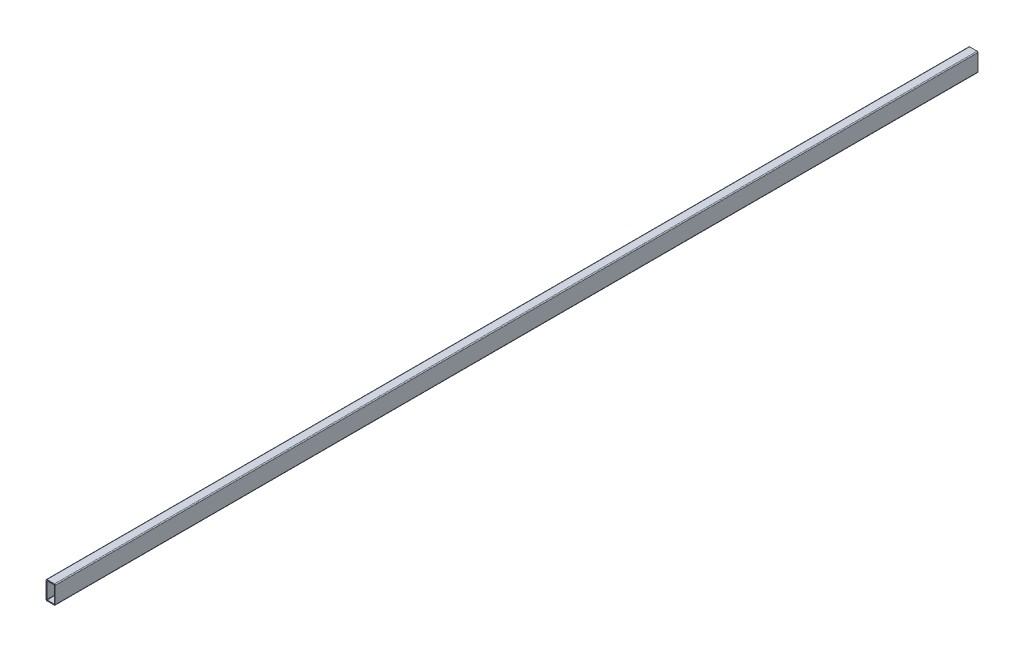
SolidWorks part; units mm, degrees
material "1.0114 (S235J0)"
ref_plane "Płaszczyzna przednia" through (0, 0, 0) normal (0, 0, 1) x (1, 0, 0)
ref_plane "Płaszczyzna górna" through (0, 0, 0) normal (0, 1, 0) x (1, 0, 0)
ref_plane "Płaszczyzna prawa" through (0, 0, 0) normal (1, 0, 0) x (0, 0, -1)
sketch "Szkic1" plane through (0, 0, 0) normal (0, 0, 1) x (1, 0, 0)
  line L0 (-7.1969, 27) -> (14.8031, 27)
  line L1 (-8.1969, -30) -> (15.8031, -30)
  line L2 (-11.1969, -27) -> (-11.1969, 27)
  line L3 (-8.1969, 30) -> (15.8031, 30)
  line L4 (18.8031, -27) -> (18.8031, 27)
  line L5 (15.8031, -26) -> (15.8031, 26)
  line L6 (-7.1969, -27) -> (14.8031, -27)
  line L7 (-8.1969, -26) -> (-8.1969, 26)
  line L8 (-11.1969, 30) -> (18.8031, 30) construction
  line L9 (18.8031, -30) -> (18.8031, 30) construction
  line L10 (-11.1969, -30) -> (18.8031, -30) construction
  line L11 (-11.1969, -30) -> (-11.1969, 30) construction
  line L12 (-8.1969, 27) -> (15.8031, 27) construction
  line L13 (15.8031, -27) -> (15.8031, 27) construction
  line L14 (-8.1969, -27) -> (15.8031, -27) construction
  line L15 (-8.1969, -27) -> (-8.1969, 27) construction
  line L16 (55, 0) -> (-55, 0) construction
  arc A0 (15.8031, 30) -> (18.8031, 27) centre (15.8031, 27) cw
  arc A1 (18.8031, -27) -> (15.8031, -30) centre (15.8031, -27) cw
  arc A2 (-8.1969, -30) -> (-11.1969, -27) centre (-8.1969, -27) cw
  arc A3 (-11.1969, 27) -> (-8.1969, 30) centre (-8.1969, 27) cw
  arc A4 (14.8031, 27) -> (15.8031, 26) centre (14.8031, 26) cw
  arc A5 (15.8031, -26) -> (14.8031, -27) centre (14.8031, -26) cw
  arc A6 (-7.1969, -27) -> (-8.1969, -26) centre (-7.1969, -26) cw
  arc A7 (-8.1969, 26) -> (-7.1969, 27) centre (-7.1969, 26) cw
  point P4 (-11.1969, 0)
  point P12 (15, 0)
  dimension "D4" = 3
  dimension "D1" = 1
  dimension "D2" = 30
  dimension "D5" = 60
  dimension "D3" = 3
extrude "Dodanie-wyciągnięcie1" add sketch "Szkic1" against normal blind 3000
sketch "Szkic2" [suppressed] plane through (0, 0, 0) normal (1, 0, 0) x (0, 0, -1)
  line L2 (0, -30) -> (16.077, 30)
  line L4 (350, 30) -> (0, 30) construction
  line L5 (16.077, 30) -> (0, 30)
  line L6 (0, 30) -> (0, -30)
  line L7 (350, 30) -> (333.923, -30)
  line L8 (350, -30) -> (0, -30) construction
  line L9 (333.923, -30) -> (350, -30)
  line L10 (350, -30) -> (350, 30)
  dimension "D1" = 15
  dimension "D2" = 15
extrude "Wytnij-wyciągnięcie1" [suppressed] cut sketch "Szkic2" against normal blind 50 and the other way blind 52
sketch "Szkic3" [suppressed] plane through (18.8031, 0, 0) normal (1, 0, 0) x (0, 0, -1)
  line L3 (16.5, 0) -> (-16.5, 0) construction
  line L6 (0, 73.9155) -> (0, -73.9155) construction
  circle A0 centre (321, 0) radius 6.25
  circle A1 centre (241, 0) radius 6.25
  dimension "D2" = 12.5
  dimension "D1" = 80
  dimension "D3" = 321
extrude "Wytnij-wyciągnięcie2" [suppressed] cut sketch "Szkic3" against normal up to surface (30 mm away)
